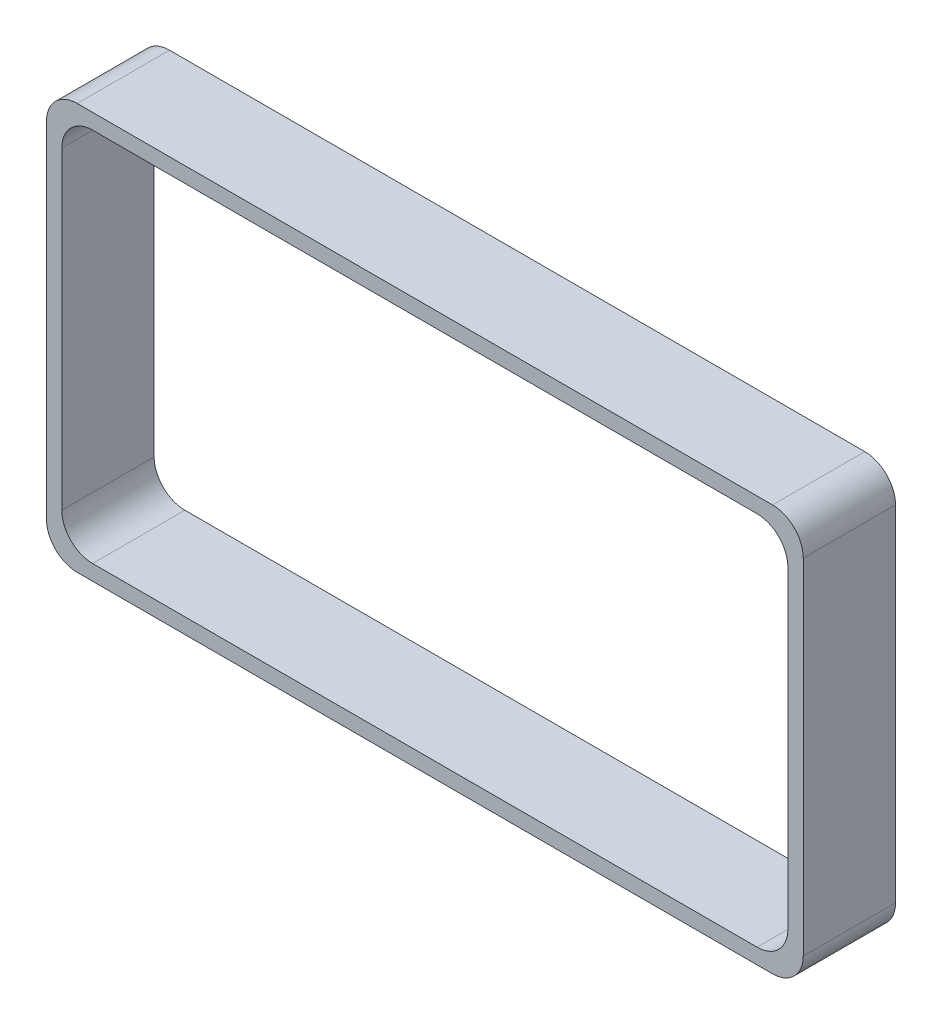
SolidWorks part; units mm, degrees
ref_plane "Plan de face" through (0, 0, 0) normal (0, 0, 1) x (1, 0, 0)
ref_plane "Plan de dessus" through (0, 0, 0) normal (0, 1, 0) x (1, 0, 0)
ref_plane "Plan de droite" through (0, 0, 0) normal (1, 0, 0) x (0, 0, -1)
sketch "Esquisse1" plane through (0, 0, 0) normal (0, 0, 1) x (1, 0, 0)
  line L1 (0, 0) -> (118, 0)
  line L2 (0, 0) -> (0, 61)
  line L3 (0, 61) -> (118, 61)
  line L4 (118, 0) -> (118, 61)
  line L5 (-2.5, -2.5) -> (120.5, -2.5)
  line L6 (-2.5, -2.5) -> (-2.5, 63.5)
  line L7 (-2.5, 63.5) -> (120.5, 63.5)
  line L8 (120.5, -2.5) -> (120.5, 63.5)
  dimension "D1" = 118
  dimension "D2" = 61
  dimension "D3" = 123
  dimension "D4" = 2.5
  dimension "D5" = 2.5
  dimension "D6" = 66
extrude "Boss.-Extru.1" add sketch "Esquisse1" along normal blind 15
fillet "Congé1" radius 5 4 edges at (0, 0, 7.5) (118, 0, 7.5) (118, 61, 7.5) (0, 61, 7.5)
fillet "Congé2" radius 5 4 edges at (120.5, 63.5, 7.5) (120.5, -2.5, 7.5) (-2.5, -2.5, 7.5) (-2.5, 63.5, 7.5)
